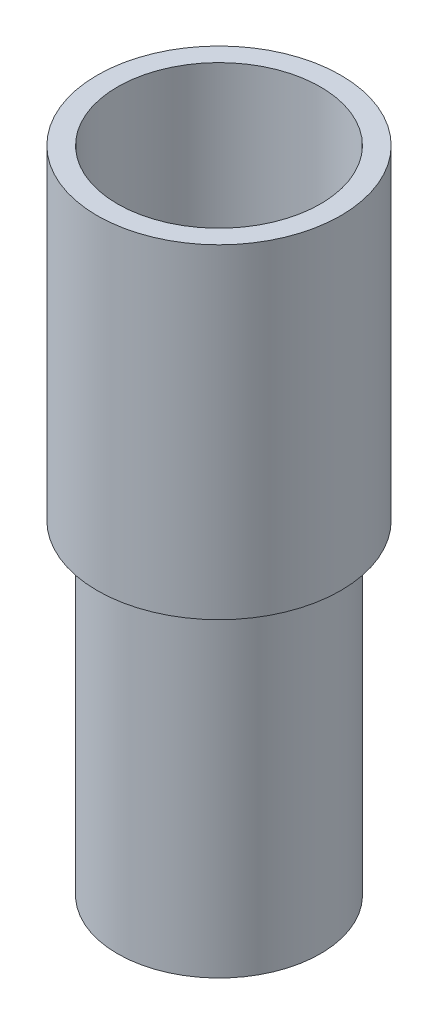
SolidWorks part; units mm, degrees
material "6061-T4 (SS)"
ref_plane "Front Plane" through (0, 0, 0) normal (0, 0, 1) x (1, 0, 0)
ref_plane "Top Plane" through (0, 0, 0) normal (0, 1, 0) x (1, 0, 0)
ref_plane "Right Plane" through (0, 0, 0) normal (1, 0, 0) x (0, 0, -1)
sketch "Sketch1" plane through (0, 0, 0) normal (0, 0, 1) x (1, 0, 0)
  line L0 (-9.525, 25.4) -> (-9.525, 0)
  line L1 (-9.525, 0) -> (-7.9375, 0)
  line L2 (-7.9375, 0) -> (-7.9375, -25.4)
  line L3 (0, -15.8578) -> (0, 15.6451) construction
  dimension "D1" = 15.875
  dimension "D2" = 19.05
  dimension "D3" = 25.4
  dimension "D4" = 25.4
sketch "Sketch2" plane through (0, 0, 0) normal (0, 1, 0) x (1, 0, 0)
  circle A0 centre (0, 0) radius 9.525
  circle A1 centre (0, 0) radius 7.9375
extrude "Boss-Extrude1" add sketch "Sketch2" along normal up to vertex (25.4 mm away) contours A0 A1 | A1 | A1 | A0 region at (-9.2556, 0, 0) region at (0, 0, 0) up to point (-9.525, 25.4, 0)
extrude "Boss-Extrude2" add sketch "Sketch2<3>" against normal up to vertex (25.4 mm away) contours A1 region at (0, 0, 0) up to point (-7.9375, -25.4, 0)
sketch "Sketch2<3>" plane through (0, 0, 0) normal (0, 1, 0) x (1, 0, 0) same geometry as "Sketch2"
sketch "Sketch7" plane through (0, 25.4, 0) normal (0, 1, 0) x (1, 0, 0)
  point P0 (0, 0)
hole_wizard "5/8 (0.625) Diameter Hole1" positions "Sketch7" profile "Sketch6" hole size "5/8" standard "ANSI Inch"
sketch "Sketch6" plane through (0, 25.4, 0) normal (1, 0, 0) x (0, 0, 1)
  line L0 (0, 0) -> (0, 25.4)
  line L1 (0, 25.4) -> (7.9375, 20.6307)
  line L2 (7.9375, 20.6307) -> (7.9375, 0)
  line L5 (7.9375, 0) -> (0, 0)
  line L10 (0, 25.4) -> (-7.9375, 20.6307) construction
  line L11 (0, -6.35) -> (0, 107.95) construction
  dimension "Hole Dia." = 15.875
  dimension "Hole Depth" = 25.4
  dimension "Drill Angle" = 118
sketch "Sketch10" plane through (0, -25.4, 0) normal (0, -1, 0) x (-1, 0, 0)
  point P0 (0, 0)
hole_wizard "1/2 (0.5) Diameter Hole1" positions "Sketch10" profile "Sketch11" hole size "1/2" standard "ANSI Inch" end condition through all
sketch "Sketch11" plane through (0, -25.4, 0) normal (1, 0, 0) x (0, 0, -1)
  line L0 (0, 0) -> (0, 50.8)
  line L1 (0, 50.8) -> (6.35, 50.8)
  line L2 (6.35, 50.8) -> (6.35, 0)
  line L5 (6.35, 0) -> (0, 0)
  line L11 (0, -6.35) -> (0, 107.95) construction
  dimension "Thru Hole Dia." = 12.7
  dimension "Thru Hole Depth" = 50.8
